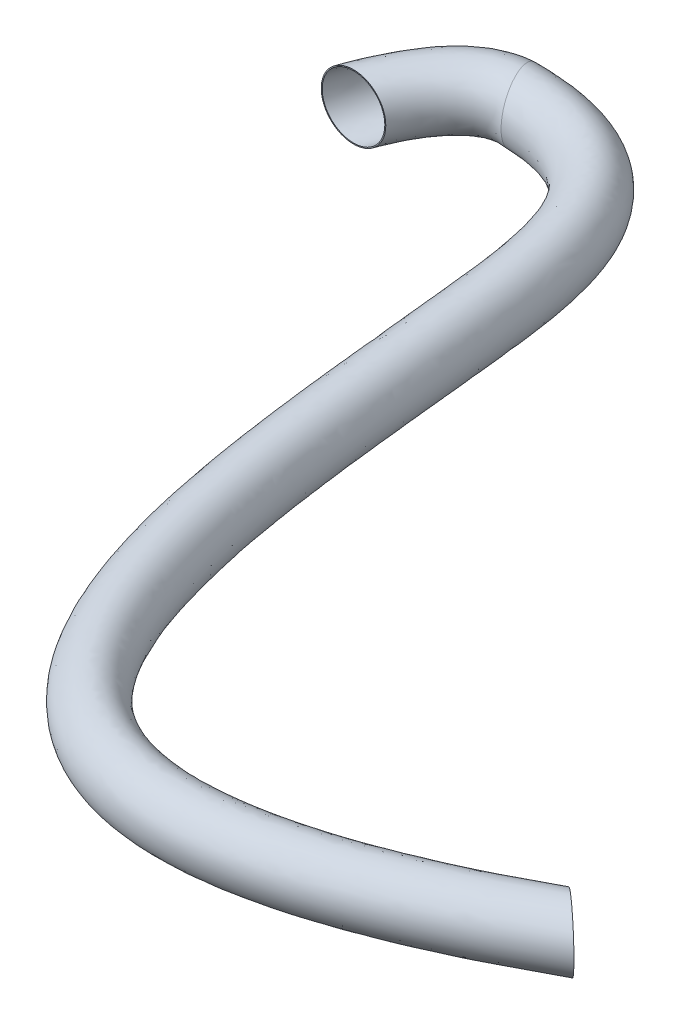
SolidWorks part; units mm, degrees
ref_plane "前视基准面" through (0, 0, 0) normal (0, 0, 1) x (1, 0, 0)
ref_plane "上视基准面" through (0, 0, 0) normal (0, 1, 0) x (1, 0, 0)
ref_plane "右视基准面" through (0, 0, 0) normal (1, 0, 0) x (0, 0, -1)
sketch "草图1" plane through (0, 0, 0) normal (0, 0, 1) x (1, 0, 0)
  circle A0 centre (0, 0) radius 95
  circle A1 centre (0, 0) radius 98
  dimension "D1" = 190
  dimension "D2" = 3
sketch "草图2" plane through (0, 0, 0) normal (0, 1, 0) x (1, 0, 0)
  spline S0 degree 3 poles (0, 0) (36.2357, 98.6068) (109.9449, 260.394) (250, 258.1114) knots 0 0 0 0 1 1 1 1
  spline S1 degree 3 poles (250, 258.1114) (436.29, 255.0754) (690.7407, 110.4367) (856.4972, -1259.0119) (909.5491, -2715.2245) (2499.1531, -1840) knots 0 0 0 0 0.105139 0.238169 1 1 1 1
  point P4 (250, 170)
  point P7 (0, 0)
  point P9 (250, 258.1114)
  dimension "D1" = 250
  dimension "D4" = 2000
sweep "扫描1" add profiles "草图1" path "草图2"
sketch "草图3" plane through (0, 0, 0) normal (0, 1, 0) x (1, 0, 0)
  line L5 (170.0065, 0) -> (190.0065, 0)
  line L6 (170.0065, 0) -> (170.0065, 20)
  line L7 (170.0065, 20) -> (190.0065, 20)
  line L8 (190.0065, 0) -> (190.0065, 20)
  dimension "D1" = 20
  dimension "D2" = 20
ref_plane "基准面1" through (46.7493, 0, -125.0835) normal (0.3501, 0, -0.9367) x (-0.9367, 0, -0.3501)
sketch "草图4" plane through (46.7493, 0, -125.0835) normal (0.3501, 0, -0.9367) x (-0.9367, 0, -0.3501)
  line L1 (-216.1657, 133.8744) -> (334.8403, 133.8744)
  line L2 (-216.1657, 133.8744) -> (-216.1657, -179.9436)
  line L3 (-216.1657, -179.9436) -> (334.8403, -179.9436)
  line L4 (334.8403, 133.8744) -> (334.8403, -179.9436)
extrude "切除-拉伸1" [suppressed] cut sketch "草图4" along normal through all contours L1 L4 L3 L2
ref_plane "基准面2" through (12.0692, 0, -66.7671) normal (0.1779, 0, -0.9841) x (-0.9841, 0, -0.1779)
sketch "草图5" plane through (12.0692, 0, -66.7671) normal (0.1779, 0, -0.9841) x (-0.9841, 0, -0.1779)
  line L1 (-146.7205, 124.8995) -> (123.5376, 124.8995)
  line L2 (-146.7205, 124.8995) -> (-146.7205, -139.0889)
  line L3 (-146.7205, -139.0889) -> (123.5376, -139.0889)
  line L4 (123.5376, 124.8995) -> (123.5376, -139.0889)
extrude "切除-拉伸2" [suppressed] cut sketch "草图5" against normal through all
